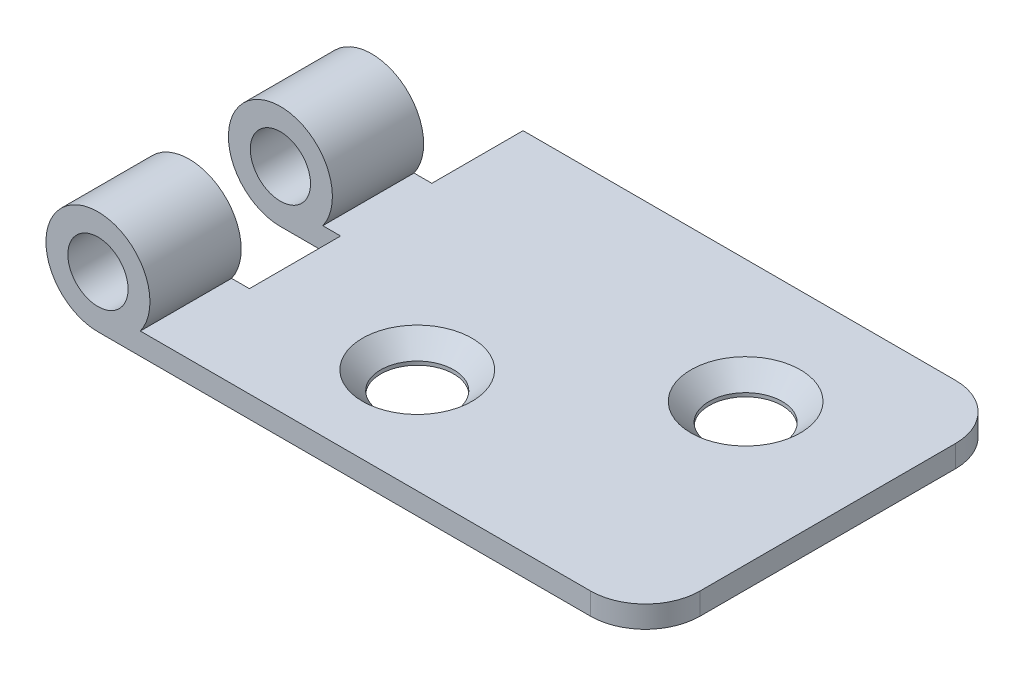
SolidWorks part; units mm, degrees
ref_plane "Plan de face" through (0, 0, 0) normal (0, 0, 1) x (1, 0, 0)
ref_plane "Plan de dessus" through (0, 0, 0) normal (0, 1, 0) x (1, 0, 0)
ref_plane "Plan de droite" through (0, 0, 0) normal (1, 0, 0) x (0, 0, -1)
sketch "Esquisse1" plane through (0, 0, 0) normal (0, 0, 1) x (1, 0, 0)
  line L0 (30, -1.65) -> (2.3238, -1.65)
  line L1 (30, -1.65) -> (30, -2.85)
  line L2 (30, -2.85) -> (0, -2.85)
  circle A0 centre (0, 0) radius 1.65
  arc A2 (2.3238, -1.65) -> (0, -2.85) centre (0, 0) ccw
  dimension "D2" = 2.85
  dimension "D1" = 1.2
  dimension "D3" = 30
extrude "Boss.-Extru.1" add sketch "Esquisse1" along normal blind 20
sketch "Esquisse2" plane through (0, -1.65, 0) normal (0, 1, 0) x (1, 0, 0)
  line L0 (30, 0) -> (2.3238, 0) construction
  line L1 (3.3, 0) -> (-7.652, 0)
  line L2 (3.3, 0) -> (3.3, -5)
  line L3 (3.3, -5) -> (-7.652, -5)
  line L4 (-7.652, 0) -> (-7.652, -5)
  line L5 (3.3, -10) -> (-7.652, -10)
  line L6 (3.3, -10) -> (3.3, -15)
  line L7 (3.3, -15) -> (-7.652, -15)
  line L8 (-7.652, -10) -> (-7.652, -15)
  line L9 (30, -20) -> (30, 0) construction
  dimension "D1" = 5
  dimension "D2" = 5
  dimension "D3" = 5
  dimension "D4" = 26.7
extrude "Enlèv. mat.-Extru.3" cut sketch "Esquisse2" against normal blind 20 and the other way blind 20
fillet "Congé1" radius 3 2 edges at (30, -2.25, 0) (30, -2.25, 20)
hole_wizard "Dégagement M41" positions "Esquisse4" profile "Esquisse3" hole size "M4" standard "Ansi Metric"
sketch "Esquisse4" plane through (0, -1.65, 0) normal (0, 1, 0) x (1, 0, 0)
  line L0 (30, -17) -> (30, -3) construction
  line L1 (27, -20) -> (2.3238, -20) construction
  line L2 (27, 0) -> (3.3, 0) construction
  point P0 (11.75, -14.25)
  point P2 (22.25, -6.75)
  dimension "D1" = 7.75
  dimension "D2" = 18.25
  dimension "D3" = 5.75
  dimension "D4" = 6.75
sketch "Esquisse3" plane through (11.75, -1.65, 14.25) normal (1, 0, 0) x (0, 0, 1)
  line L0 (0, 0) -> (0, 11.2017)
  line L1 (0, 11.2017) -> (2, 10)
  line L2 (2, 10) -> (2, 1)
  line L3 (2, 1) -> (3, 0)
  line L5 (3, 0) -> (0, 0)
  line L6 (-2, 1) -> (-3, 0) construction
  line L10 (0, 11.2017) -> (-2, 10) construction
  line L11 (0, -6.35) -> (0, 107.95) construction
  dimension "Diamètre du perçage" = 4
  dimension "Profondeur du perçage" = 10
  dimension "Diamètre du fraisage entrant" = 6
  dimension "Angle du fraisage entrant" = 90
  dimension "Angle de pointe" = 118
